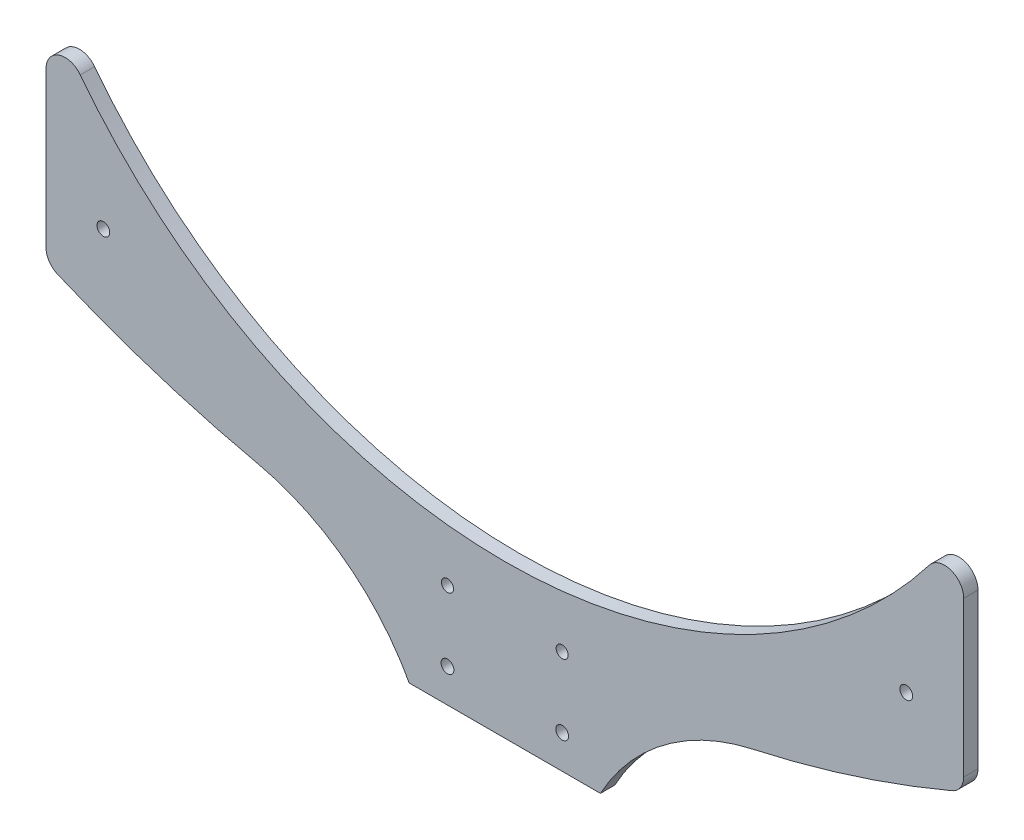
SolidWorks part; units mm, degrees
ref_plane "Front Plane" through (0, 0, 0) normal (0, 0, 1) x (1, 0, 0)
ref_plane "Top Plane" through (0, 0, 0) normal (0, 1, 0) x (1, 0, 0)
ref_plane "Right Plane" through (0, 0, 0) normal (1, 0, 0) x (0, 0, -1)
sketch "Sketch1" plane through (0, 0, 0) normal (0, 0, 1) x (1, 0, 0)
  line L0 (0, 0) -> (0, -76.2)
  line L1 (304.8, 0) -> (304.8, -76.2)
  line L2 (152.4, -1108.0077) -> (152.4, 48891.9923) construction
  line L3 (-847.6, -108.0077) -> (49152.4, -108.0077) construction
  arc A0 (0, 0) -> (304.8, 0) centre (152.4, 91.581) ccw
  arc A2 (0, -76.2) -> (304.8, -76.2) centre (152.4, 272.9923) ccw
  circle A3 centre (19.05, -57.2077) radius 2.125
  circle A4 centre (285.75, -57.2077) radius 2.125
  point P10 (152.4, -108.0077)
  dimension "D2" = 177.8
  dimension "D3" = 381
  dimension "D4" = 304.8
  dimension "D6" = 4.25
  dimension "D1" = 304.8
  dimension "D5" = 76.2
  dimension "D7" = 133.35
  dimension "D8" = 50.8
extrude "Boss-Extrude1" add sketch "Sketch1" along normal blind 4.7625
fillet "Fillet1" radius 6.35 2 edges at (304.8, 0, 2.3813) (0, 0, 2.3813)
fillet "Fillet2" radius 6.35 2 edges at (0, -76.2, 2.3813) (304.8, -76.2, 2.3813)
sketch "Sketch3" plane through (0, 0, 4.7625) normal (0, 0, 1) x (1, 0, 0)
  line L0 (0, -64.478) -> (304.8, -64.478) construction
  line L1 (0, -20.5824) -> (0, -72.0179) construction
  line L2 (304.8, -72.0179) -> (304.8, -20.5824) construction
  line L3 (152.4, -1064.478) -> (152.4, 48935.522) construction
  line L5 (120.65, -86.219) -> (184.15, -86.219)
  line L6 (120.65, -86.219) -> (120.65, -137.019)
  line L7 (120.65, -137.019) -> (184.15, -137.019)
  line L8 (184.15, -86.219) -> (184.15, -137.019)
  arc A0 (11.3862, -16.7147) -> (293.4138, -16.7147) centre (152.4, 91.581) ccw construction
  point P9 (152.4, -64.478)
  point P13 (152.4, -86.219)
  dimension "D1" = 63.5
  dimension "D2" = 50.8
extrude "Boss-Extrude2" add sketch "Sketch3" against normal up to surface (4.7625 mm away) up to face at (152.4, -58.3771, 0)
fillet "Fillet3" radius 76.2 2 edges at (184.15, -106.6825, 2.3813) (120.65, -106.6825, 2.3813)
sketch "Sketch8" plane through (0, 0, 0) normal (0, 0, -1) x (-1, 0, 0)
  line L0 (-152.4, -1162.419) -> (-152.4, 48837.581) construction
  line L1 (-184.15, -137.019) -> (-120.65, -137.019) construction
  circle A0 centre (-171.45, -125.9023) radius 2.125
  circle A1 centre (-133.35, -125.9023) radius 2.125
  circle A2 centre (-171.45, -125.9023) radius 2.85 construction
  point P7 (-152.4, -137.019)
  dimension "D1" = 4.25
extrude "Cut-Extrude3" cut sketch "Sketch8" against normal blind 19.05
sketch "Sketch10" plane through (0, 0, 4.7625) normal (0, 0, 1) x (1, 0, 0)
  circle A0 centre (133.35, -102.619) radius 2
  circle A1 centre (171.45, -102.619) radius 2
  dimension "D1" = 4
extrude "Cut-Extrude7" cut sketch "Sketch10" against normal through all
